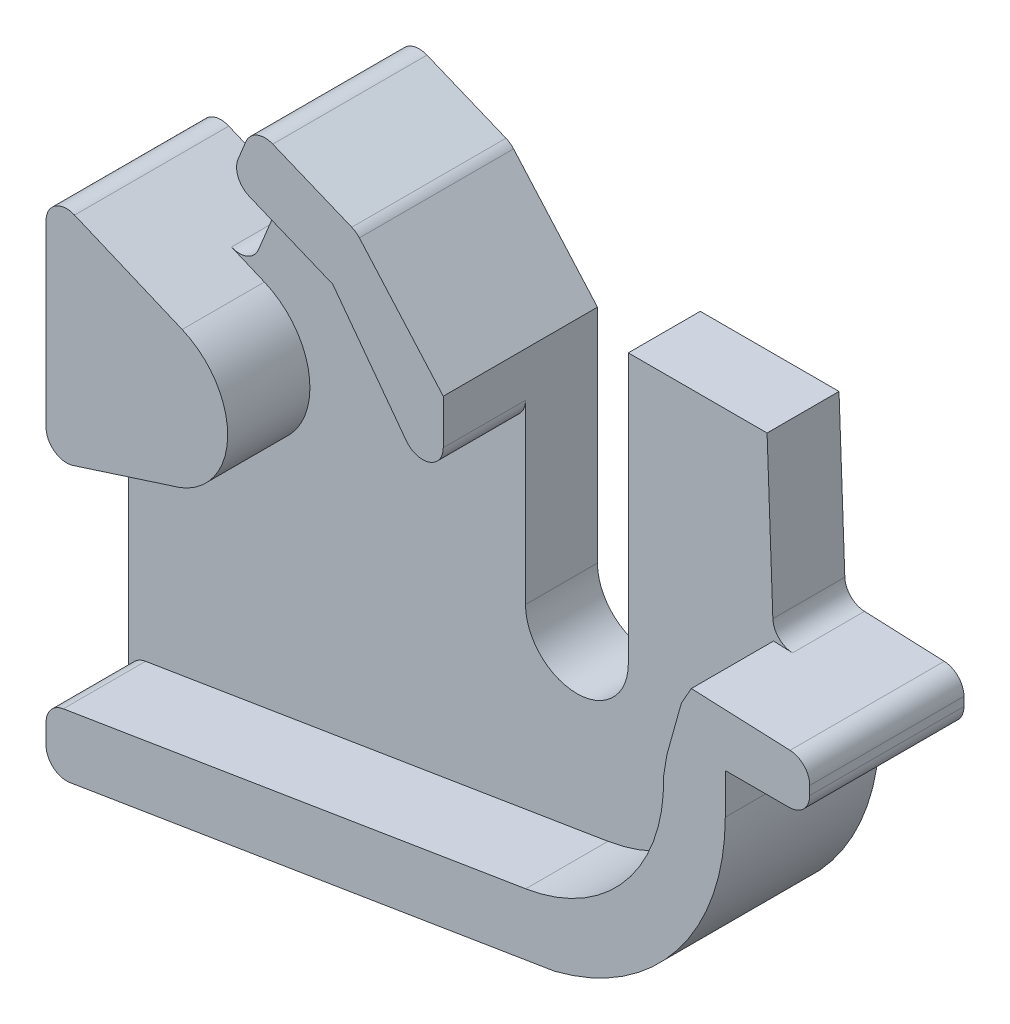
SolidWorks part; units mm, degrees
ref_plane "Front Plane" through (0, 0, 0) normal (0, 0, 1) x (1, 0, 0)
ref_plane "Top Plane" through (0, 0, 0) normal (0, 1, 0) x (1, 0, 0)
ref_plane "Right Plane" through (0, 0, 0) normal (1, 0, 0) x (0, 0, -1)
sketch "Sketch1" plane through (0, 0, 0) normal (0, 0, 1) x (1, 0, 0)
  line L0 (-48.8998, -64.1664) -> (-34.4801, 53.9567) construction
  line L3 (0, 51.4823) -> (78.4652, 51.4823)
  line L4 (78.4652, 0) -> (78.4652, 51.4823)
  line L5 (-0.9054, 14.8469) -> (9.0946, 14.8469)
  line L6 (9.0946, 14.8469) -> (9.0946, -2.1531)
  line L7 (9.0946, -2.1531) -> (-0.9054, -2.1531)
  line L8 (-0.9054, -2.1531) -> (-0.9054, 14.8469)
  line L9 (-11.6542, 28.4583) -> (-0.9054, 14.02)
  line L10 (-52.5896, 45.2866) -> (-11.6542, 28.4583)
  line L11 (9.0946, 14.8469) -> (9.0946, 29.052)
  line L12 (9.0946, 29.052) -> (22.5946, 29.052)
  line L13 (-61.5112, 32.1478) -> (-26.3036, 17.3197)
  line L14 (-26.3036, 17.3197) -> (-29.1124, 10.6505)
  line L15 (-29.1124, 10.6505) -> (-31.9213, 3.9813)
  line L16 (-70.304, -10.1797) -> (-26.4323, 3.9286)
  line L17 (-39.5424, 22.8954) -> (-39.5424, -0.2874)
  line L18 (-26.4323, 3.9286) -> (-29.1124, 10.6505)
  line L19 (-29.1124, 10.6505) -> (-31.7926, 17.3724)
  line L20 (-74.2907, -26.3461) -> (-1.036, -14.4136)
  line L21 (-1.036, -14.4136) -> (7.1186, -13.0853)
  line L22 (23.2246, 11.8381) -> (22.2572, 10.123)
  line L23 (23.2246, 11.8381) -> (34.7443, 11.3546)
  line L24 (-0.9054, 14.8469) -> (-0.9054, 20.5391)
  line L25 (-19.3381, 38.1043) -> (-8.9222, 33.8224)
  line L26 (-11.6542, 28.4583) -> (-9.3728, 34.0076)
  line L27 (-7.3088, 22.6214) -> (-2.496, 26.2043)
  line L28 (-2.496, 26.2043) -> (-9.3728, 34.0076)
  line L29 (-70.3938, -25.7113) -> (-69.6167, -30.4821)
  line L30 (-39.5424, -20.686) -> (-39.5424, -26.686)
  line L31 (26.529, 2.6512) -> (26.529, -15.9236)
  line L32 (27.019, 6.583) -> (34.7443, 6.583)
  line L33 (34.7443, 6.583) -> (34.7443, 11.3546)
  line L34 (-11.6542, 28.4583) -> (-8.9222, 28.4583)
  line L35 (-70.3938, -25.7113) -> (-70.304, -10.1797)
  line L36 (22.5946, 29.052) -> (23.2246, 11.8381)
  line L37 (-39.5424, -0.2874) -> (-39.5424, -20.686)
  line L38 (-39.5424, 22.8954) -> (-39.5424, 39.923)
  line L39 (22.2572, 10.123) -> (21.4546, 7.2463)
  line L40 (21.4546, 7.2463) -> (20.8501, 5.08)
  line L41 (20.8501, 5.08) -> (20.5233, 3.0772)
  line L42 (-8.9222, 28.4583) -> (-8.9222, 25.2921)
  line L43 (-19.3381, 38.1043) -> (-21.6194, 32.5549)
  line L44 (-0.9054, 20.5391) -> (-0.9054, 24.0677)
  line L45 (-2.496, 26.2043) -> (-0.9054, 24.3993)
  line L46 (-21.6194, 32.5549) -> (-27.6495, 17.8865)
  line L47 (-39.5424, -26.686) -> (29.4812, -15.4427)
  line L48 (4.5907, 2.6512) -> (20.529, 2.6512) construction
  line L49 (20.529, 2.6512) -> (26.529, 2.6512) construction
  line L50 (26.529, 2.6512) -> (26.529, 6.583)
  line L51 (26.529, 6.583) -> (27.019, 6.583)
  line L52 (-0.9054, 24.3993) -> (-0.9054, 24.0677)
  circle A0 centre (4.0946, 2.8469) radius 5
  circle A1 centre (4.0946, 9.8469) radius 5
  circle A2 centre (-29.1124, 10.6505) radius 7.2365
  circle A3 centre (4.5907, 2.6512) radius 15.9383
  circle A4 centre (4.5907, 2.6512) radius 21.9383
  dimension "D4" = 13.5
  dimension "D1" = 119
  dimension "D2" = 10
  dimension "D3" = 17
  dimension "D5" = 18
  dimension "D6" = 6
extrude "Boss-Extrude2" add sketch "Sketch1" along normal blind 7 contours A3 L11 L6 L7 L8 L9 | A4 L9 L10 L46 L13 A2 L16 L37 L20 | A2 L13 L17 L16 | A4 L20 L30 L47 | L20 A4 L47 L23 L22 L39 L40 L41 A3 L21 | L9 A4 L20 L21 A3 | L36 A4 L11 A3 L41 L40 L39 L22 | A4 L36 L12 L11 | A4 L50 L51 L32 L33 L23 | A0 L8 L7 | A0 L7 L6 | L44 A4 L9 A3 L24 | A4 L44 L27 L9 | L27 L28 L26 L9 | L25 L43 L10 L26 | L24 A3 L9 L8 | A2 region at (-1.579, 16.1313, 0) region at (-1.3516, 11.9334, 0) region at (-2.9873, 20.47, 0) region at (-10.9359, -2.5746, 0) region at (16.5875, 16.24, 0) region at (7.9778, -1.0363, 0) region at (0.2115, -1.0363, 0) region at (-23.6463, 1.6944, 0) region at (-3.9237, 23.8565, 0) region at (17.0739, -7.9868, 0) region at (17.2134, 24.4198, 0) region at (-7.5395, 27.8934, 0) region at (-20.9546, -20.8236, 0) region at (-15.4961, 33.2813, 0) region at (30.0023, 9.1107, 0) region at (-36.3421, 11.3624, 0)
extrude "Boss-Extrude3" add sketch "Sketch1<7>" along normal blind 15 contours A2 L13 L17 L16 | L25 L43 L10 L26 | L27 L28 L26 L9 | A4 L44 L27 L9 | L44 A4 L9 A3 L24 | L24 A3 L9 L8 | A4 L20 L30 L47 | L20 A4 L47 L23 L22 L39 L40 L41 A3 L21 | A4 L50 L51 L32 L33 L23 | A2 region at (-1.579, 16.1313, 0) region at (-2.9873, 20.47, 0) region at (-3.9237, 23.8565, 0) region at (17.0739, -7.9868, 0) region at (-7.5395, 27.8934, 0) region at (-20.9546, -20.8236, 0) region at (-15.4961, 33.2813, 0) region at (30.0023, 9.1107, 0) region at (-36.3421, 11.3624, 0)
sketch "Sketch1<7>" plane through (0, 0, 0) normal (0, 0, 1) x (1, 0, 0) same geometry as "Sketch1"
fillet "Fillet1" radius 2 12 edges at (-39.5424, -20.686, 11) (-39.5424, -0.2874, 11) (-39.5424, -26.686, 7.5) (34.7443, 6.583, 7.5) (34.7443, 11.3546, 7.5) (-0.9054, 14.02, 11) (-21.6194, 32.5549, 11) (-19.3381, 38.1043, 7.5) (-39.5424, 22.8954, 7.5) (-27.6495, 17.8865, 3.5) (23.2246, 11.8381, 3.5) (-9.3728, 34.0076, 7.5)
